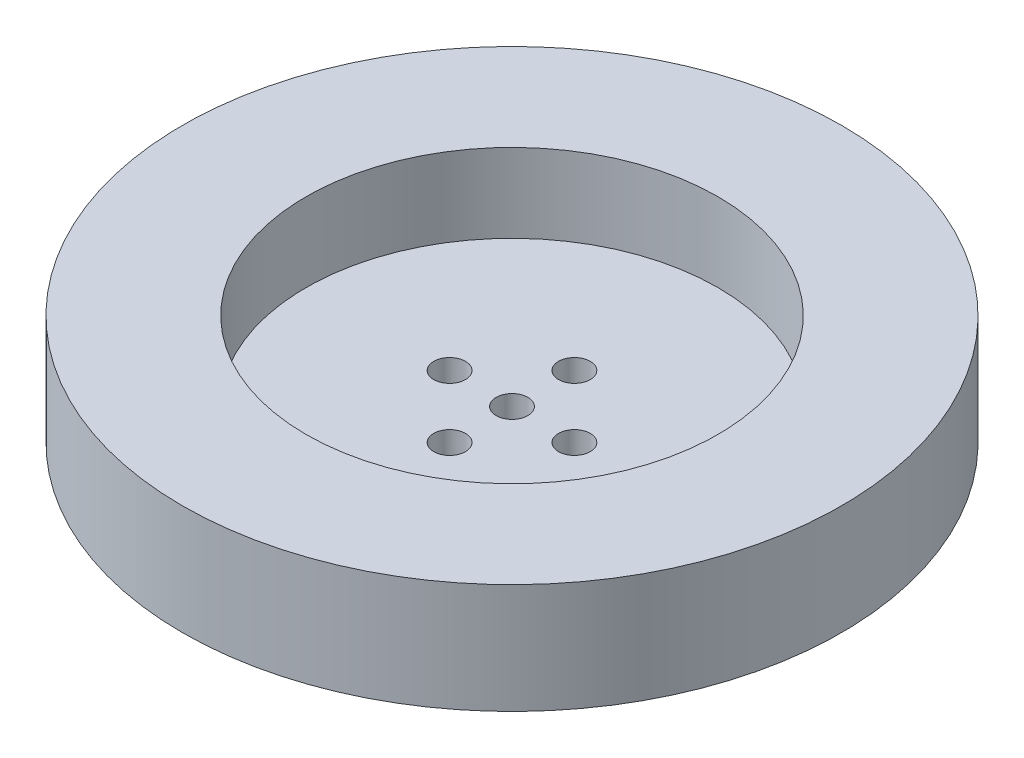
SolidWorks part; units mm, degrees
material "Alloy Steel"
ref_plane "Front Plane" through (0, 0, 0) normal (0, 0, 1) x (1, 0, 0)
ref_plane "Top Plane" through (0, 0, 0) normal (0, 1, 0) x (1, 0, 0)
ref_plane "Right Plane" through (0, 0, 0) normal (1, 0, 0) x (0, 0, -1)
sketch "Sketch1" plane through (0, 0, 0) normal (0, 1, 0) x (1, 0, 0)
  circle A0 centre (0, 0) radius 22.86
  dimension "D1" = 45.72
extrude "Boss-Extrude1" add sketch "Sketch1" along normal blind 6.35
hole_wizard "M2 Clearance Hole1" positions "Sketch3" profile "Sketch2" hole size "M2" standard "ISO" end condition through all
sketch "Sketch3" plane through (0, 6.35, 0) normal (0, 1, 0) x (1, 0, 0)
  line L1 (0, -4.3285) -> (4.3285, 0) construction
  line L2 (0, -4.3285) -> (-4.3285, 0) construction
  line L3 (-4.3285, 0) -> (0, 4.3285) construction
  line L4 (4.3285, 0) -> (0, 4.3285) construction
  line L5 (0, -4.3285) -> (0, 4.3285) construction
  line L6 (-4.3285, 0) -> (4.3285, 0) construction
  point P5 (0, 0)
  point P6 (0, 4.3285)
  point P73 (0, -4.3285)
  point P74 (-4.3285, 0)
  point P75 (4.3285, 0)
  dimension "D1" = 6.1214
sketch "Sketch2" plane through (0, 6.35, 0) normal (1, 0, 0) x (0, 0, 1)
  line L0 (0, 0) -> (0, 6.35)
  line L1 (0, 6.35) -> (1.1, 6.35)
  line L2 (1.1, 6.35) -> (1.1, 0)
  line L5 (1.1, 0) -> (0, 0)
  line L11 (0, -6.35) -> (0, 107.95) construction
  dimension "Thru Hole Dia." = 2.2
  dimension "Thru Hole Depth" = 6.35
sketch "Sketch4" plane through (0, 6.35, 0) normal (0, 1, 0) x (1, 0, 0)
  circle A0 centre (0, 0) radius 14.2875
  dimension "D1" = 28.575
extrude "Cut-Extrude1" cut sketch "Sketch4" against normal offset from surface (4.191 mm away) 2.159 up to face at (0, 0, 1.1)
sketch "Sketch6" plane through (0, 6.35, 0) normal (0, 1, 0) x (1, 0, 0)
  circle A0 centre (0, 0) radius 14.2875 construction
  circle A1 centre (0, 0) radius 22.86
  circle A2 centre (0, 0) radius 22.86
  circle A3 centre (0, 0) radius 14.2875
  dimension "D1" = 0
extrude "Boss-Extrude2" add sketch "Sketch6" along normal offset from surface (7.62 mm away) 7.62 from surface up to face at (0, 0, 1.1) starting at face at (0, 0, 1.1)
sketch "Sketch7" plane through (0, 0, 0) normal (0, -1, 0) x (1, 0, 0)
  circle A0 centre (0, 0) radius 5.6261
  circle A1 centre (0, 0) radius 12.827
  dimension "D1" = 11.2522
  dimension "D2" = 25.654
extrude "Cut-Extrude3" cut sketch "Sketch7" against normal blind 0.254
